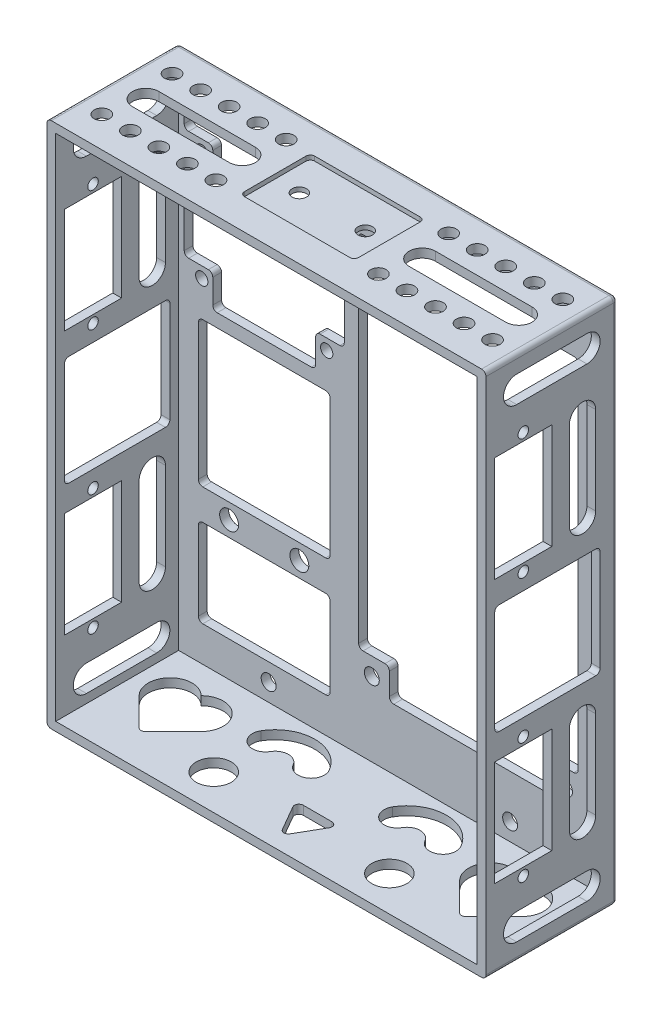
SolidWorks part; units mm, degrees
ref_plane "前视基准面" through (0, 0, 0) normal (0, 0, 1) x (1, 0, 0)
ref_plane "上视基准面" through (0, 0, 0) normal (0, 1, 0) x (1, 0, 0)
ref_plane "右视基准面" through (0, 0, 0) normal (1, 0, 0) x (0, 0, -1)
other "Configuration Table"
sketch "草图1" plane through (0, 0, 0) normal (0, 0, 1) x (1, 0, 0)
  line L5 (50, 0) -> (0, 0)
  line L6 (0, 0) -> (0, 120)
  line L7 (0, 120) -> (100, 120)
  line L8 (50, 120) -> (50, 0) construction
  line L11 (100, 0) -> (100, 120)
  line L12 (50, 0) -> (100, 0)
  dimension "D3" = 120
  dimension "D4" = 100
extrude "凸台-拉伸1" add sketch "草图1" along normal blind 30
shell "抽壳1" thickness 2 removed face at (50, 60, 30)
sketch "草图2" plane through (0, 0, 0) normal (0, 0, -1) x (-1, 0, 0)
  line L0 (-90, 109) -> (-90, 18.9) construction
  line L1 (-46, 18.9) -> (-90, 18.9) construction
  line L2 (-90, 109) -> (-46, 109) construction
  line L3 (-46, 109) -> (-46, 18.9) construction
  line L5 (-100, 0) -> (-100, 120) construction
  line L6 (-100, 120) -> (0, 120) construction
  circle A0 centre (-90, 18.9) radius 1.7
  circle A1 centre (-90, 109) radius 1.7
  circle A2 centre (-46, 109) radius 1.7
  circle A3 centre (-46, 18.9) radius 1.7
  dimension "D1" = 3.4
  dimension "D3" = 44
  dimension "D4" = 11
  dimension "D2" = 90.1
  dimension "D5" = 10
extrude "切除-拉伸1" cut sketch "草图2" against normal blind 30
sketch "草图3" plane through (0, 0, 0) normal (0, 0, -1) x (-1, 0, 0)
  line L0 (-29.5, 33.5) -> (-13.5, 33.5) construction
  line L1 (-21.5, 33.5) -> (-21.5, 20) construction
  line L2 (-36.5, 10) -> (-6.5, 10)
  line L3 (-36.5, 10) -> (-36.5, 30)
  line L4 (-36.5, 30) -> (-6.5, 30)
  line L5 (-6.5, 10) -> (-6.5, 30)
  line L6 (-36.5, 10) -> (-6.5, 30) construction
  line L7 (-36.5, 30) -> (-6.5, 10) construction
  line L8 (-21.5, 53.5) -> (-21.5, 33.5) construction
  line L9 (-36.5, 37) -> (-6.5, 37)
  line L10 (-36.5, 37) -> (-36.5, 70)
  line L11 (-36.5, 70) -> (-6.5, 70)
  line L12 (-6.5, 37) -> (-6.5, 70)
  line L13 (-36.5, 37) -> (-6.5, 70) construction
  line L14 (-36.5, 70) -> (-6.5, 37) construction
  line L15 (0, 120) -> (0, 0) construction
  line L18 (0, 0) -> (-100, 0) construction
  circle A0 centre (-29.5, 33.5) radius 2.15
  circle A1 centre (-13.5, 33.5) radius 2.15
  point P6 (-21.5, 20)
  point P12 (-21.5, 53.5)
  dimension "D1" = 4.3
  dimension "D2" = 16
  dimension "D3" = 3.5
  dimension "D4" = 30
  dimension "D5" = 20
  dimension "D6" = 3.5
  dimension "D7" = 30
  dimension "D8" = 33
  dimension "D9" = 10
  dimension "D10" = 21.5
extrude "切除-拉伸2" cut sketch "草图3" against normal blind 10
sketch "草图4" plane through (0, 0, 0) normal (-1, 0, 0) x (0, 0, 1)
  line L0 (21.5, 30) -> (28, 30) construction
  line L1 (15, 18) -> (28, 18)
  line L2 (15, 18) -> (15, 42)
  line L3 (15, 42) -> (28, 42)
  line L4 (28, 18) -> (28, 42)
  line L5 (15, 18) -> (28, 42) construction
  line L6 (15, 42) -> (28, 18) construction
  line L7 (21.5, 16.25) -> (21.5, 18) construction
  line L9 (30, 120) -> (30, 0) construction
  line L11 (0, 120) -> (0, 0) construction
  line L12 (30, 60) -> (0, 60) construction
  line L13 (21.5, 103.75) -> (3.8447, 101.25) construction
  line L14 (21.5, 103.75) -> (33.8447, 101.25) construction
  line L15 (21.5, 103.75) -> (21.5, 102) construction
  line L16 (15, 78) -> (28, 102) construction
  line L17 (15, 102) -> (28, 78) construction
  line L18 (21.5, 90) -> (28, 90) construction
  line L19 (28, 102) -> (28, 78)
  line L20 (15, 78) -> (28, 78)
  line L21 (15, 102) -> (15, 78)
  line L22 (15, 102) -> (28, 102)
  circle A0 centre (21.5, 16.25) radius 1.2
  circle A1 centre (21.5, 43.75) radius 1.2
  circle A2 centre (21.5, 76.25) radius 1.2
  circle A3 centre (21.5, 103.75) radius 1.2
  point P0 (21.5, 30)
  point P33 (21.5, 90)
  dimension "D3" = 2.4
  dimension "D4" = 27.5
  dimension "D1" = 24
  dimension "D2" = 13
  dimension "D5" = 60
  dimension "D6" = 2
extrude "切除-拉伸3" cut sketch "草图4" against normal through all
sketch "草图6" plane through (0, 0, 2) normal (0, 0, 1) x (1, 0, 0)
  line L0 (43, 105) -> (50, 105)
  line L1 (50, 105) -> (50, 112)
  line L2 (50, 112) -> (86, 112)
  line L3 (86, 112) -> (86, 105)
  line L4 (86, 105) -> (93, 105)
  line L12 (93, 105) -> (93, 22.9)
  line L13 (93, 63.95) -> (43, 63.95) construction
  line L14 (86, 22.9) -> (93, 22.9)
  line L15 (43, 105) -> (43, 22.9)
  line L16 (86, 15.9) -> (86, 22.9)
  line L17 (50, 15.9) -> (86, 15.9)
  line L18 (50, 22.9) -> (50, 15.9)
  line L19 (43, 22.9) -> (50, 22.9)
  circle A0 centre (90, 109) radius 1.7 construction
  circle A1 centre (46, 109) radius 1.7 construction
  circle A2 centre (90, 18.9) radius 1.7 construction
  dimension "D2" = 4
  dimension "D3" = 4
  dimension "D1" = 4
  dimension "D4" = 4
  dimension "D5" = 3
  dimension "D6" = 3
  dimension "D7" = 3
  dimension "D8" = 4
extrude "切除-拉伸4" cut sketch "草图6" against normal through all
sketch "草图7" plane through (0, 120, 0) normal (0, 1, 0) x (1, 0, 0)
  line L0 (0, 0) -> (100, -30) construction
  line L1 (37, -23) -> (63, -23)
  line L2 (37, -23) -> (37, -7)
  line L3 (37, -7) -> (63, -7)
  line L4 (63, -23) -> (63, -7)
  line L5 (37, -23) -> (63, -7) construction
  line L6 (37, -7) -> (63, -23) construction
  point P0 (50, -15)
  dimension "D1" = 26
  dimension "D2" = 16
extrude "切除-拉伸5" cut sketch "草图7" against normal blind 1
sketch "草图8" plane through (0, 119, 0) normal (0, 1, 0) x (1, 0, 0)
  line L0 (50, -7) -> (50, -23) construction
  line L1 (63, -7) -> (37, -7) construction
  line L2 (37, -23) -> (63, -23) construction
  line L3 (42.5, -15) -> (50, -15) construction
  circle A0 centre (42.5, -15) radius 1.65
  circle A1 centre (57.5, -15) radius 1.65
  dimension "D1" = 3.3
  dimension "D2" = 15
extrude "切除-拉伸6" cut sketch "草图8" against normal blind 1
fillet "圆角1" radius 1 4 edges at (63, 119.5, 23) (37, 119.5, 23) (63, 119.5, 7) (37, 119.5, 7)
sketch "草图9" plane through (0, 0, 0) normal (0, 0, -1) x (-1, 0, 0)
  line L0 (-50, 0) -> (-50, 120) construction
  line L1 (0, 0) -> (-100, 0) construction
  line L2 (-100, 120) -> (0, 120) construction
  circle A0 centre (-77.5, 6) radius 1.7
  circle A1 centre (-22.5, 6) radius 1.7
  dimension "D1" = 3.4
  dimension "D2" = 55
  dimension "D3" = 6
extrude "切除-拉伸7" cut sketch "草图9" against normal blind 3
sketch "草图11" plane through (0, 0, 0) normal (0, -1, 0) x (1, 0, 0)
  line L0 (50, 30) -> (50, 0) construction
  line L1 (0, 30) -> (100, 30) construction
  line L2 (0, 0) -> (100, 0) construction
  line L3 (35, 13) -> (35, 7) construction
  line L4 (35, 13) -> (32.4019, 11.5) construction
  line L5 (35, 13) -> (37.5981, 11.5) construction
  line L6 (65, 13) -> (62.4019, 11.5) construction
  line L7 (65, 13) -> (67.5981, 11.5) construction
  line L8 (65, 13) -> (65, 7) construction
  line L10 (50, 27) -> (45, 18.3397)
  line L11 (45, 18.3397) -> (55, 18.3397)
  line L12 (55, 18.3397) -> (50, 27)
  arc A0 (40.1962, 10) -> (29.8038, 10) centre (35, 13) cw construction
  arc A1 (27.2058, 8.5) -> (42.7942, 8.5) centre (35, 13) ccw
  arc A2 (32.4019, 11.5) -> (37.5981, 11.5) centre (35, 13) ccw
  arc A3 (32.4019, 11.5) -> (27.2058, 8.5) centre (29.8038, 10) ccw
  arc A4 (42.7942, 8.5) -> (37.5981, 11.5) centre (40.1962, 10) ccw
  arc A5 (59.8038, 10) -> (70.1962, 10) centre (65, 13) ccw construction
  arc A6 (72.7942, 8.5) -> (57.2058, 8.5) centre (65, 13) cw
  arc A7 (67.5981, 11.5) -> (62.4019, 11.5) centre (65, 13) cw
  arc A8 (67.5981, 11.5) -> (72.7942, 8.5) centre (70.1962, 10) cw
  arc A9 (57.2058, 8.5) -> (62.4019, 11.5) centre (59.8038, 10) cw
  circle A10 centre (50, 21.2265) radius 2.8868 construction
  point P3 (35, 7)
  point P25 (65, 7)
  dimension "D1" = 3
  dimension "D2" = 6
  dimension "D3" = 120
  dimension "D4" = 7
  dimension "D5" = 10
  dimension "D6" = 30
  dimension "D7" = 3
extrude "切除-拉伸8" cut sketch "草图11" against normal blind 3
sketch "草图12" plane through (0, 0, 0) normal (0, -1, 0) x (1, 0, 0)
  line L0 (6.4289, 15.4289) -> (9.9645, 11.8934) construction
  line L2 (20.5711, 15.4289) -> (13.5, 22.5)
  line L3 (13.5, 22.5) -> (6.4289, 15.4289)
  line L5 (10.7597, 8.6345) -> (15.9146, 3.4796) [skipped]
  line L6 (18.0387, 10.433) -> (23.1937, 15.5879) [skipped]
  line L7 (17.0355, 11.8934) -> (20.5711, 15.4289) construction
  line L8 (9.9645, 11.8934) -> (13.5, 8.3579) construction
  line L9 (17.0355, 11.8934) -> (13.5, 8.3579) construction
  line L10 (13.5, 22.5) -> (13.5, 8.3579) construction
  line L11 (50, 30) -> (50, 0) construction
  line L12 (0, 30) -> (100, 30) construction
  line L13 (0, 0) -> (100, 0) construction
  line L14 (86.5, 22.5) -> (86.5, 8.3579) construction
  line L15 (82.9645, 11.8934) -> (86.5, 8.3579) construction
  line L16 (90.0355, 11.8934) -> (86.5, 8.3579) construction
  line L17 (82.9645, 11.8934) -> (79.4289, 15.4289) construction
  line L18 (93.5711, 15.4289) -> (90.0355, 11.8934) construction
  line L19 (86.5, 22.5) -> (93.5711, 15.4289)
  line L20 (79.4289, 15.4289) -> (86.5, 22.5)
  arc A0 (86.5, 8.3579) -> (79.4289, 15.4289) centre (82.9645, 11.8934) cw
  arc A1 (6.4289, 15.4289) -> (13.5, 8.3579) centre (9.9645, 11.8934) ccw
  arc A2 (13.5, 8.3579) -> (20.5711, 15.4289) centre (17.0355, 11.8934) ccw
  arc A3 (93.5711, 15.4289) -> (86.5, 8.3579) centre (90.0355, 11.8934) cw
  dimension "D1" = 10
  dimension "D2" = 73
  dimension "D3" = 7.5
extrude "切除-拉伸9" cut sketch "草图12" against normal blind 3
sketch "草图13" plane through (0, 0, 0) normal (0, -1, 0) x (1, 0, 0)
  line L0 (50, 30) -> (50, 0) construction
  line L1 (0, 30) -> (100, 30) construction
  line L2 (0, 0) -> (100, 0) construction
  circle A0 centre (30, 22) radius 4
  circle A1 centre (70, 22) radius 4
  dimension "D1" = 8
  dimension "D2" = 40
  dimension "D3" = 8
extrude "切除-拉伸10" cut sketch "草图13" against normal blind 3
fillet "圆角2" radius 1 5 edges at (13.5, 1, 22.5) (50, 1, 27) (45, 1, 18.3397) (55, 1, 18.3397) (86.5, 1, 22.5)
sketch "草图14" plane through (0, 0, 0) normal (-1, 0, 0) x (0, 0, 1)
  line L2 (0, 60) -> (30, 60) construction
  line L3 (5, 47.5) -> (27, 47.5)
  line L8 (4, 48.5) -> (4, 71.5)
  line L9 (5, 72.5) -> (27, 72.5)
  line L10 (28, 48.5) -> (28, 71.5)
  line L11 (4, 47.5) -> (28, 72.5) construction
  line L12 (0, 120) -> (0, 0) construction
  line L13 (30, 120) -> (30, 0) construction
  line L16 (4, 72.5) -> (28, 47.5) construction
  arc A0 (27, 47.5) -> (28, 48.5) centre (27, 48.5) ccw
  arc A1 (5, 47.5) -> (4, 48.5) centre (5, 48.5) cw
  arc A2 (27, 72.5) -> (28, 71.5) centre (27, 71.5) cw
  arc A3 (4, 71.5) -> (5, 72.5) centre (5, 71.5) cw
  point P0 (16, 60)
  dimension "D4" = 1
  dimension "D1" = 24
  dimension "D2" = 25
  dimension "D3" = 2
extrude "切除-拉伸11" cut sketch "草图14" against normal through all
sketch "草图15" plane through (0, 120, 0) normal (0, 1, 0) x (1, 0, 0)
  line L0 (7.5, -15) -> (29.5, -15) construction
  line L1 (7.5, -12) -> (29.5, -12)
  line L2 (7.5, -18) -> (29.5, -18)
  line L3 (29.5, -15) -> (37, -15) construction
  line L4 (37, -8) -> (37, -22) construction
  line L5 (50, 0) -> (50, -30) construction
  line L6 (100, -30) -> (0, -30) construction
  line L7 (18.5, -7) -> (18.5, -15) construction
  line L9 (37, -15) -> (63, -15) construction
  line L10 (63, -22) -> (63, -8) construction
  line L11 (81.5, -7) -> (81.5, -15) construction
  line L12 (70.5, -15) -> (63, -15) construction
  line L13 (92.5, -15) -> (70.5, -15) construction
  line L14 (92.5, -12) -> (70.5, -12)
  line L15 (92.5, -18) -> (70.5, -18)
  arc A0 (7.5, -12) -> (7.5, -18) centre (7.5, -15) ccw
  arc A1 (29.5, -18) -> (29.5, -12) centre (29.5, -15) ccw
  circle A2 centre (5.5, -7) radius 1.75
  circle A3 centre (12, -7) radius 1.75
  circle A4 centre (18.5, -7) radius 1.75
  circle A5 centre (25, -7) radius 1.75
  circle A6 centre (31.5, -7) radius 1.75
  circle A7 centre (31.5, -23) radius 1.75
  circle A8 centre (25, -23) radius 1.75
  circle A9 centre (18.5, -23) radius 1.75
  circle A10 centre (12, -23) radius 1.75
  circle A11 centre (5.5, -23) radius 1.75
  circle A12 centre (94.5, -23) radius 1.75
  circle A13 centre (88, -23) radius 1.75
  circle A14 centre (81.5, -23) radius 1.75
  circle A15 centre (75, -23) radius 1.75
  circle A16 centre (68.5, -23) radius 1.75
  circle A17 centre (68.5, -7) radius 1.75
  circle A18 centre (75, -7) radius 1.75
  circle A19 centre (81.5, -7) radius 1.75
  circle A20 centre (88, -7) radius 1.75
  circle A21 centre (94.5, -7) radius 1.75
  arc A22 (92.5, -12) -> (92.5, -18) centre (92.5, -15) cw
  arc A23 (70.5, -18) -> (70.5, -12) centre (70.5, -15) cw
  point P2 (18.5, -15)
  point P63 (81.5, -15)
  dimension "D2" = 3
  dimension "D4" = 3.5
  dimension "D6" = 6.5
  dimension "D7" = 8
  dimension "D1" = 22
  dimension "D3" = 7.5
  dimension "D5" = 5
extrude "切除-拉伸12" cut sketch "草图15" against normal up to next
sketch "草图16" plane through (0, 0, 0) normal (-1, 0, 0) x (0, 0, 1)
  line L0 (7, 113) -> (23, 113) construction
  line L1 (7, 116) -> (23, 116)
  line L2 (7, 110) -> (23, 110)
  line L3 (15, 120) -> (15, 113) construction
  line L4 (30, 120) -> (0, 120) construction
  line L5 (0, 60) -> (30, 60) construction
  line L6 (0, 120) -> (0, 0) construction
  line L7 (30, 120) -> (30, 0) construction
  line L8 (15, 0) -> (15, 7) construction
  line L9 (7, 7) -> (23, 7) construction
  line L10 (7, 4) -> (23, 4)
  line L11 (7, 10) -> (23, 10)
  arc A0 (7, 116) -> (7, 110) centre (7, 113) ccw
  arc A1 (23, 110) -> (23, 116) centre (23, 113) ccw
  arc A2 (7, 4) -> (7, 10) centre (7, 7) cw
  arc A3 (23, 10) -> (23, 4) centre (23, 7) cw
  point P2 (15, 113)
  point P21 (15, 7)
  dimension "D2" = 3
  dimension "D1" = 16
  dimension "D3" = 7
extrude "切除-拉伸13" cut sketch "草图16" against normal through all
fillet "圆角4" radius 1 12 edges at (50, 112, 1) (43, 105, 1) (50, 105, 1) (43, 22.9, 1) (50, 15.9, 1) (50, 22.9, 1) (86, 112, 1) (86, 105, 1) (93, 105, 1) (86, 15.9, 1) (93, 22.9, 1) (86, 22.9, 1)
fillet "圆角5" radius 1 8 edges at (6.5, 37, 1) (36.5, 37, 1) (6.5, 70, 1) (36.5, 70, 1) (6.5, 10, 1) (6.5, 30, 1) (36.5, 30, 1) (36.5, 10, 1)
fillet "圆角6" radius 1 8 edges at (100, 120, 15) (100, 0, 15) (100, 60, 0) (0, 120, 15) (50, 120, 0) (0, 0, 15) (50, 0, 0) (0, 60, 0)
sketch "草图17" plane through (0, 0, 0) normal (-1, 0, 0) x (0, 0, 1)
  line L0 (8, 20) -> (8, 40) construction
  line L1 (5, 20) -> (5, 40)
  line L2 (11, 20) -> (11, 40)
  line L3 (8, 30) -> (15, 30) construction
  line L4 (15, 42) -> (15, 18) construction
  line L5 (30, 60) -> (1, 60) construction
  line L6 (30, 119) -> (30, 1) construction
  line L7 (1, 119) -> (1, 1) construction
  line L8 (8, 90) -> (15, 90) construction
  line L9 (8, 100) -> (8, 80) construction
  line L10 (5, 100) -> (5, 80)
  line L11 (11, 100) -> (11, 80)
  arc A0 (5, 20) -> (11, 20) centre (8, 20) ccw
  arc A1 (11, 40) -> (5, 40) centre (8, 40) ccw
  arc A2 (5, 100) -> (11, 100) centre (8, 100) cw
  arc A3 (11, 80) -> (5, 80) centre (8, 80) cw
  point P2 (8, 30)
  point P21 (8, 90)
  dimension "D2" = 3
  dimension "D1" = 20
  dimension "D3" = 7
extrude "切除-拉伸14" cut sketch "草图17" against normal through all
sketch "草图18" plane through (0, 0, 0) normal (0, 0, -1) x (-1, 0, 0)
  line L0 (-35.725, 103.02) -> (-35.725, 78) construction
  line L1 (-35.725, 78) -> (-7.275, 78) construction
  line L2 (-7.275, 78) -> (-7.275, 103.02) construction
  line L3 (-7.275, 103.02) -> (-35.725, 103.02) construction
  line L4 (-21.5, 78) -> (-21.5, 70) construction
  line L5 (-7.5, 70) -> (-35.5, 70) construction
  circle A0 centre (-35.725, 78) radius 1.4
  circle A1 centre (-7.275, 78) radius 1.4
  circle A2 centre (-35.725, 103.02) radius 1.4
  circle A3 centre (-7.275, 103.02) radius 1.4
  dimension "D1" = 2.8
  dimension "D2" = 28.45
  dimension "D3" = 25.02
  dimension "D4" = 8
extrude "切除-拉伸15" cut sketch "草图18" against normal blind 10
sketch "草图19" plane through (0, 0, 0) normal (0, 0, -1) x (-1, 0, 0)
  line L0 (-39.725, 100.52) -> (-39.725, 80.5)
  line L1 (-39.725, 80.5) -> (-33.225, 80.5)
  line L2 (-33.225, 80.5) -> (-33.225, 73)
  line L3 (-33.225, 73) -> (-9.775, 73)
  line L10 (-33.225, 105.52) -> (-33.225, 100.52)
  line L11 (-33.225, 100.52) -> (-39.725, 100.52)
  line L12 (-33.225, 105.52) -> (-39.725, 105.52)
  line L13 (-39.725, 105.52) -> (-39.725, 115.52)
  line L14 (-39.725, 115.52) -> (-3.275, 115.52)
  line L17 (-21.5, 115.52) -> (-21.5, 73) construction
  line L18 (-35.725, 103.02) -> (-7.275, 103.02) construction
  line L19 (-3.275, 105.52) -> (-3.275, 115.52)
  line L20 (-9.775, 105.52) -> (-3.275, 105.52)
  line L21 (-9.775, 100.52) -> (-3.275, 100.52)
  line L22 (-9.775, 105.52) -> (-9.775, 100.52)
  line L23 (-9.775, 80.5) -> (-9.775, 73)
  line L24 (-3.275, 80.5) -> (-9.775, 80.5)
  line L25 (-3.275, 100.52) -> (-3.275, 80.5)
  circle A1 centre (-35.725, 103.02) radius 1.4 construction
  circle A2 centre (-35.725, 78) radius 1.4 construction
  point P4 (-21.5, 103.02)
  dimension "D1" = 7.5
  dimension "D2" = 6.5
  dimension "D3" = 2.5
  dimension "D4" = 2.5
  dimension "D5" = 2.5
  dimension "D6" = 10
  dimension "D7" = 2.5
extrude "切除-拉伸16" cut sketch "草图19" against normal blind 10
fillet "圆角7" radius 1 16 edges at (3.275, 105.52, 1) (9.775, 105.52, 1) (9.775, 100.52, 1) (3.275, 100.52, 1) (3.275, 80.5, 1) (9.775, 80.5, 1) (9.775, 73, 1) (33.225, 73, 1) (33.225, 80.5, 1) (39.725, 80.5, 1) (39.725, 100.52, 1) (33.225, 100.52, 1) (33.225, 105.52, 1) (39.725, 105.52, 1) (3.275, 115.52, 1) (39.725, 115.52, 1)
